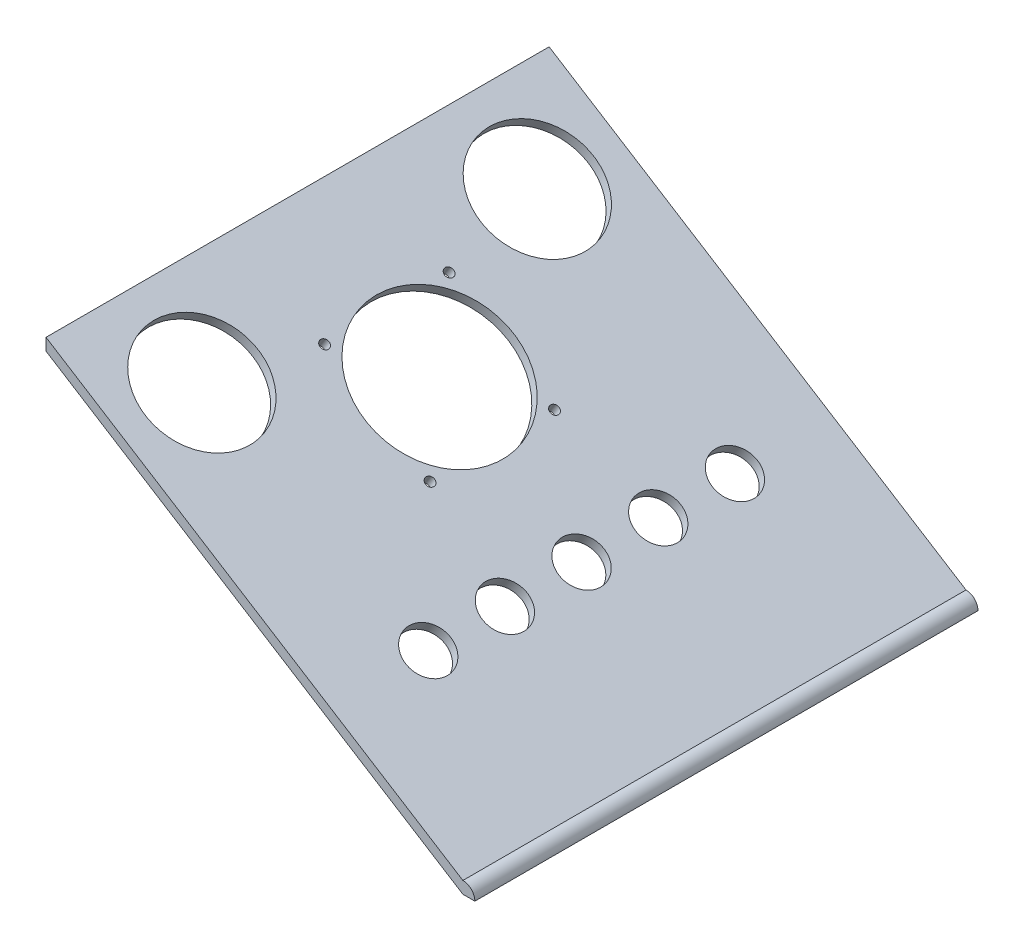
SolidWorks part; units mm, degrees
material "6061-T6 (SS)"
ref_plane "Front Plane" through (0, 0, 0) normal (0, 0, 1) x (1, 0, 0)
ref_plane "Top Plane" through (0, 0, 0) normal (0, 1, 0) x (1, 0, 0)
ref_plane "Right Plane" through (0, 0, 0) normal (1, 0, 0) x (0, 0, -1)
sketch "Sketch1" plane through (0, 0, 0) normal (0, 0, 1) x (1, 0, 0)
  line L2 (110.49, -69.425) -> (0, 0)
  line L3 (0, 0) -> (110.49, 0) construction
  line L4 (110.49, 0) -> (110.49, -66.25) construction
  line L11 (0, 0) -> (0, 3.175)
  line L12 (0, 3.175) -> (110.49, -66.25)
  line L16 (110.49, -66.25) -> (110.49, -69.425)
  dimension "D1" = 110.49
  dimension "D2" = 69.425
  dimension "D3" = 3.175
extrude "Boss-Extrude1" add sketch "Sketch1" along normal blind 133.35 contours L2 L11 L12 L16
sketch "Sketch2" plane through (1.4303, 2.2763, 0) normal (0.532, 0.8467, 0) x (0.8467, -0.532, 0)
  line L0 (-1.6892, -66.675) -> (12.815, -66.675) construction
  line L1 (-1.6892, -133.35) -> (-1.6892, 0) construction
  line L4 (26.2608, -83.175) -> (59.2608, -83.175)
  line L5 (26.2608, -83.175) -> (26.2608, -50.175)
  line L6 (26.2608, -50.175) -> (59.2608, -50.175)
  line L7 (59.2608, -83.175) -> (59.2608, -50.175)
  line L8 (26.2608, -50.175) -> (59.2608, -83.175) construction
  line L9 (23.0108, -66.675) -> (86.815, -66.675) construction
  circle A0 centre (26.2608, -83.175) radius 1.2
  circle A1 centre (26.2608, -50.175) radius 1.2
  circle A2 centre (59.2608, -83.175) radius 1.2
  circle A3 centre (59.2608, -50.175) radius 1.2
  circle A4 centre (42.7608, -66.675) radius 19.75
  point P0 (42.7608, -66.675)
  dimension "D4" = 2.4
  dimension "D5" = 2.4
  dimension "D6" = 2.4
  dimension "D7" = 2.4
  dimension "D8" = 39.5
  dimension "D2" = 33
  dimension "D3" = 33
  dimension "D9" = 44.45
extrude "Cut-Extrude1" cut sketch "Sketch2" against normal through all contours A1 | A3 | A2 | A0 | A4
sketch "Sketch3" plane through (110.49, 0, 0) normal (1, 0, 0) x (0, 0, -1)
  line L1 (-133.35, -66.25) -> (0, -66.25)
  line L2 (-133.35, -66.25) -> (-133.35, -69.425)
  line L3 (-133.35, -69.425) -> (0, -69.425)
  line L4 (0, -66.25) -> (0, -69.425)
extrude "Boss-Extrude2" add sketch "Sketch3" along normal blind 3.175
fillet "Fillet1" radius 3.175 1 edges at (113.665, -66.25, 66.675)
sketch "Sketch5" plane through (1.4303, 2.2763, 0) normal (0.532, 0.8467, 0) x (0.8467, -0.532, 0)
  line L3 (128.8017, -133.35) -> (128.8017, 0) construction
  line L4 (-1.6892, -66.675) -> (133.1792, -66.675) construction
  line L5 (-1.6892, -133.35) -> (-1.6892, 0) construction
  line L6 (133.1792, -133.35) -> (133.1792, 0) construction
  line L7 (20.8517, -22.225) -> (20.8517, -111.125) construction
  circle A0 centre (20.8517, -111.125) radius 15
  circle A1 centre (20.8517, -22.225) radius 15
  dimension "D1" = 30
  dimension "D3" = 30
  dimension "D4" = 88.9
  dimension "D5" = 0
  dimension "D6" = 107.95
sketch "Sketch6" plane through (1.4303, 2.2763, 0) normal (0.532, 0.8467, 0) x (0.8467, -0.532, 0)
  line L1 (-1.6892, -133.35) -> (-1.6892, 0) construction
  line L6 (-1.6892, 0) -> (-1.6892, -66.675) construction
  line L7 (-1.6892, -66.675) -> (87.2108, -66.675) construction
  line L8 (87.2108, -107.315) -> (87.2108, -26.035) construction
  circle A0 centre (87.2108, -46.355) radius 6
  circle A4 centre (87.2108, -26.035) radius 6
  circle A5 centre (87.2108, -86.995) radius 6
  circle A6 centre (87.2108, -107.315) radius 6
  circle A7 centre (87.2108, -66.675) radius 6
  dimension "D1" = 12
  dimension "D2" = 12
  dimension "D3" = 88.9
  dimension "D4" = 66.675
  dimension "D5" = 20.32
  dimension "D6" = 20.32
  dimension "D7" = 20.32
  dimension "D8" = 20.32
extrude "Cut-Extrude2" cut sketch "Sketch5" against normal through all
extrude "Cut-Extrude3" cut sketch "Sketch6" against normal through all
